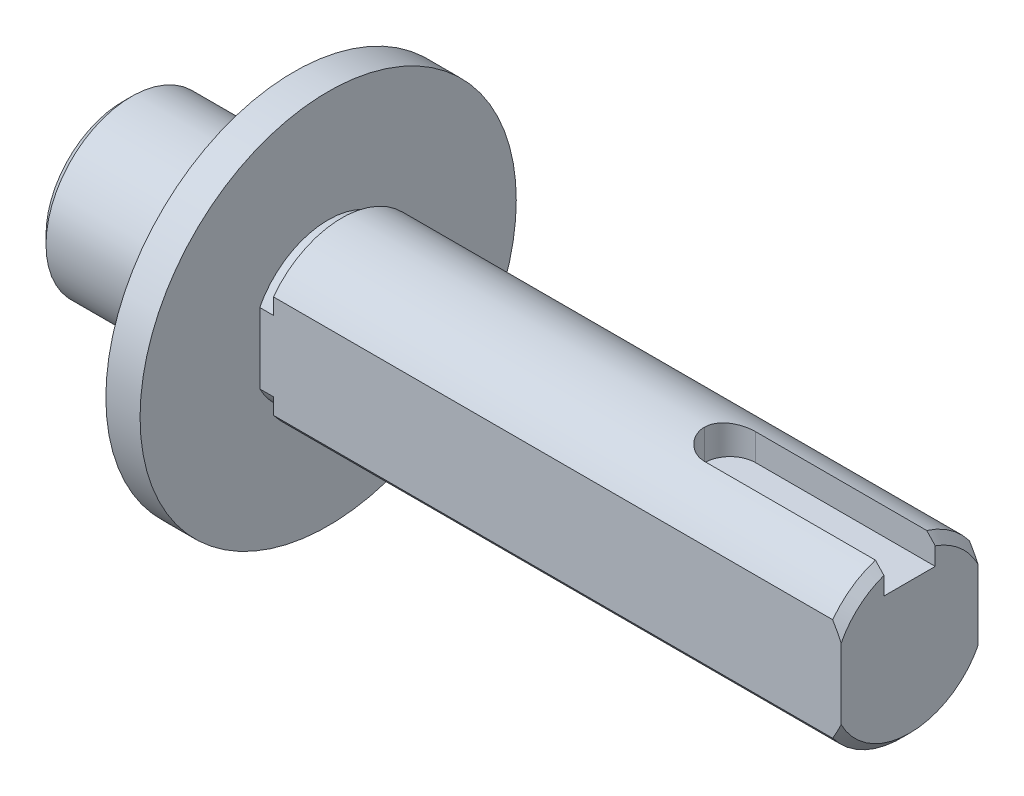
SolidWorks part; units mm, degrees
material "6061-T6 (SS)"
ref_plane "Front Plane" through (0, 0, 0) normal (0, 0, 1) x (1, 0, 0)
ref_plane "Top Plane" through (0, 0, 0) normal (0, 1, 0) x (1, 0, 0)
ref_plane "Right Plane" through (0, 0, 0) normal (1, 0, 0) x (0, 0, -1)
sketch "Sketch1" plane through (0, 0, 0) normal (1, 0, 0) x (0, 0, -1)
  circle A0 centre (0, 0) radius 5
  dimension "D1" = 10
extrude "Boss-Extrude1" add sketch "Sketch1" along normal blind 34
chamfer "Chamfer1" distance 0.5 angle 45 1 edges at (34, 0, -5)
sketch "Sketch2" plane through (0, 0, 0) normal (-1, 0, 0) x (0, 0, 1)
  circle A0 centre (0, 0) radius 11
  dimension "D1" = 22
extrude "Boss-Extrude2" add sketch "Sketch2" along normal blind 2
sketch "Sketch3" plane through (34, 0, 0) normal (1, 0, 0) x (0, 0, -1)
  line L0 (0, 0) -> (0, 3.2) construction
  line L1 (-1.5, 5) -> (1.5, 5)
  line L2 (-1.5, 5) -> (-1.5, 3.2)
  line L3 (-1.5, 3.2) -> (1.5, 3.2)
  line L4 (1.5, 5) -> (1.5, 3.2)
  line L5 (0, 0) -> (8.3936, 0) construction
  line L6 (-1.5, -3.2) -> (1.5, -3.2)
  line L7 (1.5, -5) -> (1.5, -3.2)
  line L8 (-1.5, -5) -> (1.5, -5)
  line L9 (-1.5, -5) -> (-1.5, -3.2)
  circle A0 centre (0, 0) radius 5 construction
  dimension "D1" = 3
  dimension "D2" = 1.8
extrude "Cut-Extrude1" cut sketch "Sketch3" against normal blind 12 contours L3 L4 L1 L2
fillet "Fillet1" radius 1.5 2 edges at (22, 3.9848, 1.5) (22, 3.9848, -1.5)
sketch "Sketch4" plane through (-2, 0, 0) normal (-1, 0, 0) x (0, 0, 1)
  circle A0 centre (0, 0) radius 5
  dimension "D1" = 10
extrude "Boss-Extrude3" add sketch "Sketch4" along normal blind 10
sketch "Sketch6" plane through (0, 0, 0) normal (0, 0, 1) x (1, 0, 0)
  line L0 (0, 0) -> (37.6174, 0) construction
  line L1 (-2, 5) -> (-2.8, 5)
  line L2 (-2, 5) -> (-2, 4.5)
  line L3 (-2, 4.5) -> (-2.8, 4.5)
  line L4 (-2.8, 5) -> (-2.8, 4.5)
  line L6 (0, 5) -> (0.8, 5)
  line L7 (0, 5) -> (0, 4.5)
  line L8 (0, 4.5) -> (0.8, 4.5)
  line L9 (0.8, 5) -> (0.8, 4.5)
  dimension "D1" = 0.8
  dimension "D2" = 0.5
revolve "Cut-Revolve1" cut sketch "Sketch6" angle 360 about L0
ref_plane "Plane1" through (1, 0, 0) normal (1, 0, 0) x (0, 0, -1)
chamfer "Chamfer2" distance 0.5 angle 45 1 edges at (-12, 0, 5)
sketch "Sketch7" plane through (0, 0, 0) normal (1, 0, 0) x (0, 0, -1)
  line L6 (-4, 3) -> (-4, -3)
  line L8 (4, 3) -> (4, -3)
  circle A3 centre (0, 0) radius 5 construction
  arc A4 (-4, 3) -> (-4, -3) centre (0, 0) ccw
  arc A5 (4, -3) -> (4, 3) centre (0, 0) ccw
  point P1 (0, 0)
  dimension "D1" = 8
extrude "Cut-Extrude2" cut sketch "Sketch7" along normal through all
